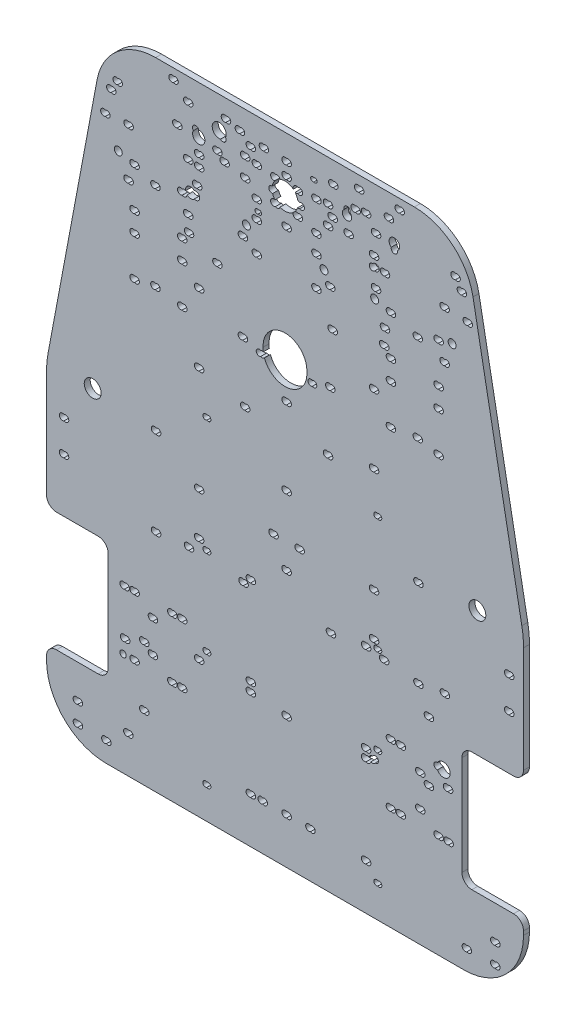
SolidWorks part; units mm, degrees
ref_plane "前视基准面" through (0, 0, 0) normal (0, 0, 1) x (1, 0, 0)
ref_plane "上视基准面" through (0, 0, 0) normal (0, 1, 0) x (1, 0, 0)
ref_plane "右视基准面" through (0, 0, 0) normal (1, 0, 0) x (0, 0, -1)
other "Configuration Table"
sketch "草图1" plane through (0, 0, 0) normal (0, 0, 1) x (1, 0, 0)
  line L0 (-120, -4.645) -> (-120, -58.035)
  line L1 (-94, -63.035) -> (-115, -63.035)
  line L2 (-119.145, 4.565) -> (-94.59, 135.53)
  line L3 (-89, -118.035) -> (-89, -68.035)
  line L4 (65.1, 160) -> (-65.1, 160)
  line L5 (-115, -123.035) -> (-94, -123.035)
  line L6 (94.59, 135.53) -> (119.145, 4.565)
  line L7 (-120, -128.035) -> (-120, -130)
  line L8 (120, -58.035) -> (120, -4.645)
  line L9 (-90, -160) -> (90, -160)
  line L10 (115, -63.035) -> (94, -63.035)
  line L11 (120, -130) -> (120, -128.035)
  line L12 (89, -68.035) -> (89, -118.035)
  line L13 (94, -123.035) -> (115, -123.035)
  arc A0 (-120, -58.035) -> (-115, -63.035) centre (-115, -58.035) ccw
  arc A1 (-119.145, 4.565) -> (-120, -4.645) centre (-70, -4.642) ccw
  arc A2 (-89, -68.035) -> (-94, -63.035) centre (-94, -68.035) ccw
  arc A3 (-65.1, 160) -> (-94.59, 135.53) centre (-65.1041, 130) ccw
  arc A4 (-94, -123.035) -> (-89, -118.035) centre (-94, -118.035) ccw
  arc A5 (94.59, 135.53) -> (65.1, 160) centre (65.1041, 130) ccw
  arc A6 (-115, -123.035) -> (-120, -128.035) centre (-115, -128.035) ccw
  arc A7 (120, -4.645) -> (119.145, 4.565) centre (70, -4.642) ccw
  arc A8 (-120, -130) -> (-90, -160) centre (-90, -130) ccw
  arc A9 (115, -63.035) -> (120, -58.035) centre (115, -58.035) ccw
  arc A10 (90, -160) -> (120, -130) centre (90, -130) ccw
  arc A11 (94, -63.035) -> (89, -68.035) centre (94, -68.035) ccw
  arc A12 (120, -128.035) -> (115, -123.035) centre (115, -128.035) ccw
  arc A13 (89, -118.035) -> (94, -123.035) centre (94, -118.035) ccw
extrude "底盘板_3mm" add sketch "草图1" along normal blind 3
sketch "草图2" plane through (0, 0, 0) normal (0, 0, 1) x (1, 0, 0)
  circle A0 centre (71.6222, -88.447) radius 1.6
  circle A1 centre (71.6222, -58.447) radius 1.6
  circle A2 centre (-18, -88.05) radius 1.6
  circle A3 centre (79.5, 99.85) radius 1.6
  circle A4 centre (-44, -38.5574) radius 1.6
  circle A5 centre (-44, -91.3574) radius 1.6
  circle A6 centre (-18, -43.55) radius 1.6
  circle A7 centre (-81.25, -100.9) radius 1.6
  circle A8 centre (49.5, 99.85) radius 1.6
  circle A9 centre (-15, 99.8501) radius 1.6
  circle A10 centre (44, -38.5574) radius 1.6
  circle A11 centre (-18, -137.05) radius 1.6
  circle A12 centre (79.6222, -44.447) radius 1.6
  circle A13 centre (79.5, 123.85) radius 1.6
  circle A14 centre (-44, 70.4426) radius 1.6
  circle A15 centre (-44, -17.0574) radius 1.6
  circle A16 centre (-15, 123.8501) radius 1.6
  circle A17 centre (44, 123.2426) radius 1.6
  circle A18 centre (5.6569, 137.8532) radius 1.6
  circle A19 centre (40, -92.55) radius 1.6
  circle A20 centre (-18, -92.55) radius 1.6
  circle A21 centre (44, -17.0574) radius 1.6
  circle A22 centre (49.5, 123.85) radius 1.6
  circle A23 centre (40, 145.2) radius 1.6
  circle A24 centre (44, -91.3574) radius 1.6
  circle A25 centre (40, -88.05) radius 1.6
  circle A26 centre (-5.6569, 137.8532) radius 1.6
  circle A27 centre (31.2, 141.8053) radius 1.6
  circle A28 centre (44, 35.7426) radius 1.6
  circle A29 centre (-79.5, 99.8501) radius 1.6
  circle A30 centre (15, 138.85) radius 1.6
  circle A31 centre (-6.5532, 131.7498) radius 1.6
  circle A32 centre (-79.6222, -141.3529) radius 1.6
  circle A33 centre (36.5, 153.85) radius 1.6
  circle A34 centre (40, -137.05) radius 1.6
  circle A35 centre (44, 70.4426) radius 1.6
  circle A36 centre (-5.6569, 126.5394) radius 1.6
  circle A37 centre (15, 123.85) radius 1.6
  circle A38 centre (-18, 145.2) radius 1.6
  circle A39 centre (-23.5, 149.4184) radius 1.6
  circle A40 centre (5.6569, 126.5394) radius 1.6
  circle A41 centre (45, 138.85) radius 1.6
  circle A42 centre (-79.5, 123.8501) radius 1.6
  circle A43 centre (15, 99.85) radius 1.6
  circle A44 centre (40, -43.55) radius 1.6
  circle A45 centre (-15, 138.85) radius 1.6
  circle A46 centre (6.5532, 131.7498) radius 1.6
  circle A47 centre (-71.6222, -127.3529) radius 1.6
  circle A48 centre (-71.6222, -97.3529) radius 1.6
  circle A49 centre (55, 136.201) radius 1.6
  circle A50 centre (81.25, -84.9) radius 1.6
  circle A51 centre (-49.5, 148.85) radius 1.6
  circle A52 centre (-30.5, 150.85) radius 1.6
  circle A53 centre (-44, 123.2426) radius 1.6
  circle A54 centre (15, 114.85) radius 1.6
  circle A55 centre (0, 132.1963) radius 4
  circle A56 centre (-20.8597, 130.0559) radius 1.6
  circle A57 centre (0, 119.1612) radius 1.6
  circle A58 centre (23.5, 149.4184) radius 1.6
  circle A59 centre (-44, 35.7426) radius 1.6
  circle A60 centre (31.2, 131.8058) radius 1.6
  circle A61 centre (51.5, 148.85) radius 1.6
  circle A62 centre (-14, 118.5695) radius 1.1
  circle A63 centre (20.8597, 130.0559) radius 1.6
  circle A64 centre (-34.7189, 144.2392) radius 1.6
  circle A65 centre (-49.5, 123.8501) radius 1.6
  circle A66 centre (45, 114.85) radius 1.6
  circle A67 centre (-55, 136.201) radius 1.6
  circle A68 centre (-45, 114.85) radius 1.6
  circle A69 centre (14.0014, 146.5709) radius 1.1
  circle A70 centre (0.0007, 147.5702) radius 1.6
  circle A71 centre (-31.2, 141.8053) radius 1.6
  circle A72 centre (34.7189, 144.2392) radius 1.6
  circle A73 centre (44, 128.7426) radius 1.6
  circle A74 centre (-11.4, 147.9509) radius 1.6
  circle A75 centre (-20.8597, 139.5559) radius 1.6
  circle A76 centre (46, -85.9817) radius 1.35
  circle A77 centre (105, -140) radius 1.6
  circle A78 centre (-15, 114.85) radius 1.6
  circle A79 centre (-45, 138.85) radius 1.6
  circle A80 centre (20.8597, 139.5559) radius 1.6
  circle A81 centre (-31.2, 131.8058) radius 1.6
  circle A82 centre (-40, -85.9817) radius 1.35
  circle A83 centre (-85, 140) radius 1.6
  circle A84 centre (85, 140) radius 1.6
  circle A85 centre (-40, -143.9817) radius 1.35
  circle A86 centre (46, 16.0183) radius 1.35
  circle A87 centre (46, -143.9817) radius 1.35
  circle A88 centre (-105, -140) radius 1.6
  circle A89 centre (96.7802, 0) radius 4.25
  circle A90 centre (46, -41.9817) radius 1.35
  circle A91 centre (-81.5003, -78.0344) radius 1.6
  circle A92 centre (-57.5003, -78.0343) radius 1.6
  circle A93 centre (52.5, -77.9) radius 1.6
  circle A94 centre (-76.5, -107.9) radius 1.6
  circle A95 centre (-40, -41.9817) radius 1.35
  circle A96 centre (-52.5, -107.9) radius 1.6
  circle A97 centre (-81.5001, -108.0344) radius 1.6
  circle A98 centre (57.5001, -108.0343) radius 1.6
  circle A99 centre (67.25, -84.9) radius 1.6
  circle A100 centre (-96.7802, 0) radius 4.25
  circle A101 centre (-52.5, -77.9) radius 1.6
  circle A102 centre (-76.5, -77.9) radius 1.6
  circle A103 centre (81.5001, -108.0344) radius 1.6
  circle A104 centre (67.25, -100.9) radius 1.6
  circle A105 centre (76.5, -77.9) radius 1.6
  circle A106 centre (81.5003, -78.0344) radius 1.6
  circle A107 centre (12, -137.0155) radius 1.6
  circle A108 centre (-67.25, -84.9) radius 1.6
  circle A109 centre (-57.5001, -108.0343) radius 1.6
  circle A110 centre (-40, 16.0183) radius 1.35
  circle A111 centre (112, -36.0494) radius 1.6
  circle A112 centre (-90.691, -150) radius 1.6
  circle A113 centre (105, -150) radius 1.6
  circle A114 centre (112, -19.9702) radius 1.6
  circle A115 centre (-67.25, -100.9) radius 1.6
  circle A116 centre (0, -137.0155) radius 1.6
  circle A117 centre (-105, -150) radius 1.6
  circle A118 centre (91.157, 123.1269) radius 1.6
  circle A119 centre (-112, -36.0494) radius 1.6
  circle A120 centre (22, 60.2034) radius 1.6
  circle A121 centre (76.5, -107.9) radius 1.6
  circle A122 centre (23.202, 134.9205) radius 1.6
  circle A123 centre (-112, -19.9702) radius 1.6
  circle A124 centre (56.9, 155) radius 1.6
  circle A125 centre (-91.157, 123.1269) radius 1.6
  circle A126 centre (66.3284, -46.618) radius 1.6
  circle A127 centre (90.691, -150) radius 1.6
  circle A128 centre (-65.6716, -46.618) radius 1.6
  circle A129 centre (-66, 60.2034) radius 1.6
  circle A130 centre (-56.9, 155) radius 1.6
  circle A131 centre (88.2, 134.9846) radius 1.6
  circle A132 centre (-22, 60.2034) radius 1.6
  circle A133 centre (66.3284, -2.618) radius 1.6
  circle A134 centre (57.5003, -78.0343) radius 1.6
  circle A135 centre (23.202, 85.9205) radius 1.6
  circle A136 centre (-88.2, 134.9846) radius 1.6
  circle A137 centre (22, 104.2034) radius 1.6
  circle A138 centre (52.5, 108.1) radius 1.6
  circle A139 centre (76.5, 58.1) radius 1.6
  circle A140 centre (-66, 104.2034) radius 1.6
  circle A141 centre (66, 60.2034) radius 1.6
  circle A142 centre (-76.5, 108.1) radius 1.6
  circle A143 centre (52.5, 78.1) radius 1.6
  circle A144 centre (76.5, 78.1) radius 1.6
  circle A145 centre (-12, -137.0155) radius 1.6
  circle A146 centre (-76.5, 88.1) radius 1.6
  circle A147 centre (76.5, 88.1) radius 1.6
  circle A148 centre (-76.5, 58.1) radius 1.6
  circle A149 centre (-34.798, 85.9205) radius 1.6
  circle A150 centre (52.5, -107.9) radius 1.6
  circle A151 centre (76.5, 108.1) radius 1.6
  circle A152 centre (-52.5, 88.1) radius 1.6
  circle A153 centre (49.1, 92.0723) radius 1.6
  circle A154 centre (-52.5, 58.1) radius 1.6
  circle A155 centre (-65.6716, -2.618) radius 1.6
  circle A156 centre (-52.5, 78.1) radius 1.6
  circle A157 centre (0, 61.5723) radius 11
  circle A158 centre (66, 104.2034) radius 1.6
  circle A159 centre (-52.5, 108.1) radius 1.6
  circle A160 centre (-83.8997, 109.9166) radius 2
  circle A161 centre (-76.5, 78.1) radius 1.6
  circle A162 centre (-49.1, 92.0723) radius 1.6
  circle A163 centre (-20.8597, 30.2366) radius 1.6
  circle A164 centre (6.5532, -17.9502) radius 1.6
  circle A165 centre (52.5, 88.1) radius 1.6
  circle A166 centre (-22, 104.2034) radius 1.6
  circle A167 centre (-44.9, 109.9168) radius 2
  circle A168 centre (0, -94.0277) radius 1.6
  circle A169 centre (-34.798, 134.9205) radius 1.6
  circle A170 centre (12.9911, 57.4701) radius 1.5
  circle A171 centre (19.6002, 109.9172) radius 2
  circle A172 centre (20.8597, 30.2366) radius 1.6
  circle A173 centre (-6.5532, -17.9502) radius 1.6
  circle A174 centre (0, 4.1723) radius 1.6
  circle A175 centre (0, 42.9723) radius 1.6
  circle A176 centre (0, -30.5388) radius 1.6
  circle A177 centre (-44, 128.7426) radius 1.6
  circle A178 centre (-49.5, 99.8501) radius 1.6
  circle A179 centre (-21.6716, -46.618) radius 1.6
  circle A180 centre (0, 141.1723) radius 1.6
  circle A181 centre (-49.1, -44.9277) radius 1.6
  circle A182 centre (52.5, 58.1) radius 1.6
  circle A183 centre (45.1002, 109.9173) radius 2
  circle A184 centre (-12.9897, 57.4702) radius 1.5
  circle A185 centre (84.0999, 109.9175) radius 2
  circle A186 centre (22.3284, -46.618) radius 1.6
  circle A187 centre (49.1, -44.9277) radius 1.6
  circle A188 centre (-19.3995, 109.917) radius 2
extrude "切除-拉伸3" cut sketch "草图2" along normal through all
sketch "草图741" plane through (0, 0, 0) normal (0, 0, 1) x (1, 0, 0)
  circle A0 centre (73.2222, -88.447) radius 1.6
  circle A1 centre (71.6222, -88.447) radius 1.6 construction
  circle A2 centre (73.2222, -58.447) radius 1.6
  circle A3 centre (71.6222, -58.447) radius 1.6 construction
  circle A4 centre (-16.4, -88.05) radius 1.6
  circle A5 centre (-18, -88.05) radius 1.6 construction
  circle A6 centre (81.1, 99.85) radius 1.6
  circle A7 centre (79.5, 99.85) radius 1.6 construction
  circle A8 centre (-42.4, -38.5574) radius 1.6
  circle A9 centre (-44, -38.5574) radius 1.6 construction
  circle A10 centre (-42.4, -91.3574) radius 1.6
  circle A11 centre (-44, -91.3574) radius 1.6 construction
  circle A12 centre (-16.4, -43.55) radius 1.6
  circle A13 centre (-18, -43.55) radius 1.6 construction
  circle A14 centre (-79.65, -100.9) radius 1.6
  circle A15 centre (-81.25, -100.9) radius 1.6 construction
  circle A16 centre (51.1, 99.85) radius 1.6
  circle A17 centre (49.5, 99.85) radius 1.6 construction
  circle A18 centre (-13.4, 99.8501) radius 1.6
  circle A19 centre (-15, 99.8501) radius 1.6 construction
  circle A20 centre (45.6, -38.5574) radius 1.6
  circle A21 centre (44, -38.5574) radius 1.6 construction
  circle A22 centre (-16.4, -137.05) radius 1.6
  circle A23 centre (-18, -137.05) radius 1.6 construction
  circle A24 centre (81.2222, -44.447) radius 1.6
  circle A25 centre (79.6222, -44.447) radius 1.6 construction
  circle A26 centre (81.1, 123.85) radius 1.6
  circle A27 centre (79.5, 123.85) radius 1.6 construction
  circle A28 centre (-42.4, 70.4426) radius 1.6
  circle A29 centre (-44, 70.4426) radius 1.6 construction
  circle A30 centre (-42.4, -17.0574) radius 1.6
  circle A31 centre (-44, -17.0574) radius 1.6 construction
  circle A32 centre (-13.4, 123.8501) radius 1.6
  circle A33 centre (-15, 123.8501) radius 1.6 construction
  circle A34 centre (45.6, 123.85) radius 1.7114
  circle A35 centre (7.2569, 137.8532) radius 1.6
  circle A36 centre (5.6569, 137.8532) radius 1.6 construction
  circle A37 centre (41.6, -92.55) radius 1.6
  circle A38 centre (40, -92.55) radius 1.6 construction
extrude "切除-拉伸741" cut sketch "草图741" along normal through all
sketch "草图742" plane through (0, 0, 0) normal (0, 0, 1) x (1, 0, 0)
  circle A0 centre (-16.4, -92.55) radius 1.6
  circle A1 centre (-18, -92.55) radius 1.6 construction
  circle A2 centre (45.6, -17.0574) radius 1.6
  circle A3 centre (44, -17.0574) radius 1.6 construction
  circle A4 centre (51.1, 123.85) radius 1.6
  circle A5 centre (49.5, 123.85) radius 1.6 construction
  circle A6 centre (41.6, 145.2) radius 1.6
  circle A7 centre (40, 145.2) radius 1.6 construction
  circle A8 centre (45.4329, -90.6454) radius 1.6
  arc A9 (43.1891, -92.7367) -> (42.4109, -91.1707) centre (44, -91.3574) ccw construction
  circle A10 centre (41.6, -88.05) radius 1.6
  circle A11 centre (40, -88.05) radius 1.6 construction
  circle A12 centre (-4.0569, 137.8532) radius 1.6
  circle A13 centre (-5.6569, 137.8532) radius 1.6 construction
  circle A14 centre (31.2, 139.4532) radius 2.3521
  circle A15 centre (45.6, 35.7426) radius 1.6
  circle A16 centre (-77.9, 99.8501) radius 1.6
  circle A17 centre (-79.5, 99.8501) radius 1.6 construction
  circle A18 centre (16.6, 138.85) radius 1.6
  circle A19 centre (15, 138.85) radius 1.6 construction
  circle A20 centre (-4.9532, 131.7498) radius 1.6
  circle A21 centre (-6.5532, 131.7498) radius 1.6 construction
  circle A22 centre (-78.0222, -141.3529) radius 1.6
  circle A23 centre (-79.6222, -141.3529) radius 1.6 construction
  circle A24 centre (38.1, 153.85) radius 1.6
  circle A25 centre (36.5, 153.85) radius 1.6 construction
  circle A26 centre (41.6, -137.05) radius 1.6
  circle A27 centre (45.6, 70.4426) radius 1.6
  circle A28 centre (44, 70.4426) radius 1.6 construction
  circle A29 centre (-4.0569, 126.5394) radius 1.6
  circle A30 centre (-5.6569, 126.5394) radius 1.6 construction
  circle A31 centre (16.6, 123.85) radius 1.6
  circle A32 centre (15, 123.85) radius 1.6 construction
  circle A33 centre (-16.4, 145.2) radius 1.6
  circle A34 centre (-18, 145.2) radius 1.6 construction
  circle A35 centre (-21.9, 149.4184) radius 1.6
  circle A36 centre (-23.5, 149.4184) radius 1.6 construction
extrude "切除-拉伸742" cut sketch "草图742" along normal through all
sketch "草图744" plane through (0, 0, 0) normal (0, 0, 1) x (1, 0, 0)
  circle A0 centre (7.2569, 126.5394) radius 1.6
  circle A1 centre (5.6569, 126.5394) radius 1.6 construction
  circle A2 centre (46.6, 138.85) radius 1.6
  circle A3 centre (45, 138.85) radius 1.6 construction
  circle A4 centre (-77.9, 123.8501) radius 1.6
  circle A5 centre (-79.5, 123.8501) radius 1.6 construction
  circle A6 centre (16.6, 99.85) radius 1.6
  circle A7 centre (15, 99.85) radius 1.6 construction
  circle A8 centre (41.6, -43.55) radius 1.6
  circle A9 centre (40, -43.55) radius 1.6 construction
  circle A10 centre (-13.4, 138.85) radius 1.6
  circle A11 centre (-15, 138.85) radius 1.6 construction
  circle A12 centre (8.1532, 131.7498) radius 1.6
  circle A13 centre (6.5532, 131.7498) radius 1.6 construction
  circle A14 centre (-70.0222, -127.3529) radius 1.6
  circle A15 centre (-71.6222, -127.3529) radius 1.6 construction
  circle A16 centre (-70.0222, -97.3529) radius 1.6
  circle A17 centre (-71.6222, -97.3529) radius 1.6 construction
  circle A18 centre (55, 138.85) radius 2.649
extrude "切除-拉伸744" cut sketch "草图744" along normal through all
sketch "草图745" plane through (0, 0, 0) normal (0, 0, 1) x (1, 0, 0)
  circle A0 centre (82.85, -84.9) radius 1.6
  circle A1 centre (81.25, -84.9) radius 1.6 construction
  circle A2 centre (-47.9, 148.85) radius 1.6
  circle A3 centre (-49.5, 148.85) radius 1.6 construction
  circle A4 centre (-28.9, 150.85) radius 1.6
  circle A5 centre (-30.5, 150.85) radius 1.6 construction
  circle A6 centre (-42.4, 123.2426) radius 1.6
  circle A7 centre (-44, 123.2426) radius 1.6 construction
  circle A8 centre (16.6, 114.85) radius 1.6
  circle A9 centre (15, 114.85) radius 1.6 construction
  circle A10 centre (0, 132.1963) radius 6.5684
  circle A11 centre (-19.2597, 130.0559) radius 1.6
  circle A12 centre (-20.8597, 130.0559) radius 1.6 construction
  circle A13 centre (1.6, 119.1612) radius 1.6
  circle A14 centre (0, 119.1612) radius 1.6 construction
  circle A15 centre (25.1, 149.4184) radius 1.6
  circle A16 centre (23.5, 149.4184) radius 1.6 construction
  circle A17 centre (-42.4, 35.7426) radius 1.6
  circle A18 centre (-44, 35.7426) radius 1.6 construction
extrude "切除-拉伸745" cut sketch "草图745" along normal through all
sketch "草图746" plane through (0, 0, 0) normal (0, 0, 1) x (1, 0, 0)
  circle A0 centre (32.8, 131.8058) radius 1.6
  circle A1 centre (31.2, 131.8058) radius 1.6 construction
  circle A2 centre (53.1, 148.85) radius 1.6
  circle A3 centre (51.5, 148.85) radius 1.6 construction
  circle A4 centre (-12.9, 118.5695) radius 1.1
  circle A5 centre (-14, 118.5695) radius 1.1 construction
  circle A6 centre (22.4597, 130.0559) radius 1.6
  circle A7 centre (20.8597, 130.0559) radius 1.6 construction
  circle A8 centre (-33.1189, 144.2392) radius 1.6
  circle A9 centre (-34.7189, 144.2392) radius 1.6 construction
  circle A10 centre (-47.9, 123.8501) radius 1.6
  circle A11 centre (-49.5, 123.8501) radius 1.6 construction
  circle A12 centre (46.6, 114.85) radius 1.6
  circle A13 centre (45, 114.85) radius 1.6 construction
  circle A14 centre (-53.4, 136.201) radius 1.6
  circle A15 centre (-55, 136.201) radius 1.6 construction
  circle A16 centre (-43.4, 114.85) radius 1.6
  circle A17 centre (-45, 114.85) radius 1.6 construction
  circle A18 centre (15.1014, 146.5709) radius 1.1
  circle A19 centre (14.0014, 146.5709) radius 1.1 construction
  circle A20 centre (1.6007, 147.5702) radius 1.6
  circle A21 centre (0.0007, 147.5702) radius 1.6 construction
  circle A22 centre (-33.1189, 144.2392) radius 3.5189
  circle A23 centre (36.3189, 144.2392) radius 1.6
  circle A24 centre (34.7189, 144.2392) radius 1.6 construction
  circle A25 centre (45.6, 128.7426) radius 1.6
  circle A26 centre (44, 128.7426) radius 1.6 construction
  circle A27 centre (-9.8, 147.9509) radius 1.6
  circle A28 centre (-11.4, 147.9509) radius 1.6 construction
  circle A29 centre (-19.2597, 139.5559) radius 1.6
  circle A30 centre (-20.8597, 139.5559) radius 1.6 construction
  circle A31 centre (47.35, -85.9817) radius 1.35
  circle A32 centre (46, -85.9817) radius 1.35 construction
  circle A33 centre (106.6, -140) radius 1.6
  circle A34 centre (105, -140) radius 1.6 construction
  circle A35 centre (-13.4, 114.85) radius 1.6
  circle A36 centre (-15, 114.85) radius 1.6 construction
  circle A37 centre (-43.4, 136.201) radius 3.0947
extrude "切除-拉伸746" cut sketch "草图746" along normal through all
sketch "草图747" plane through (0, 0, 0) normal (0, 0, 1) x (1, 0, 0)
  circle A0 centre (22.4597, 139.5559) radius 1.6
  circle A1 centre (20.8597, 139.5559) radius 1.6 construction
  circle A2 centre (-29.6, 131.8058) radius 1.6
  circle A3 centre (-31.2, 131.8058) radius 1.6 construction
  circle A4 centre (-38.65, -85.9817) radius 1.35
  circle A5 centre (-40, -85.9817) radius 1.35 construction
  circle A6 centre (-83.4, 140) radius 1.6
  circle A7 centre (-85, 140) radius 1.6 construction
  circle A8 centre (86.6, 140) radius 1.6
  circle A9 centre (85, 140) radius 1.6 construction
  circle A10 centre (-38.65, -143.9817) radius 1.35
  circle A11 centre (-40, -143.9817) radius 1.35 construction
  circle A12 centre (47.35, 16.0183) radius 1.35
  circle A13 centre (46, 16.0183) radius 1.35 construction
  circle A14 centre (47.35, -143.9817) radius 1.35
  circle A15 centre (46, -143.9817) radius 1.35 construction
  circle A16 centre (-103.4, -140) radius 1.6
  circle A17 centre (-105, -140) radius 1.6 construction
  circle A18 centre (96.7802, 0) radius 4.25
  circle A19 centre (47.35, -41.9817) radius 1.35
  circle A20 centre (46, -41.9817) radius 1.35 construction
  circle A21 centre (-79.9003, -78.0344) radius 1.6
  circle A22 centre (-81.5003, -78.0344) radius 1.6 construction
  circle A23 centre (-55.9003, -78.0343) radius 1.6
  circle A24 centre (-57.5003, -78.0343) radius 1.6 construction
  circle A25 centre (54.1, -77.9) radius 1.6
  circle A26 centre (52.5, -77.9) radius 1.6 construction
  circle A27 centre (-74.9, -107.9) radius 1.6
  circle A28 centre (-76.5, -107.9) radius 1.6 construction
  circle A29 centre (-38.65, -41.9817) radius 1.35
  circle A30 centre (-40, -41.9817) radius 1.35 construction
  circle A31 centre (-50.9, -107.9) radius 1.6
  circle A32 centre (-52.5, -107.9) radius 1.6 construction
  circle A33 centre (59.1001, -108.0343) radius 1.6
  circle A34 centre (57.5001, -108.0343) radius 1.6 construction
  circle A35 centre (68.85, -84.9) radius 1.6
  circle A36 centre (67.25, -84.9) radius 1.6 construction
extrude "切除-拉伸747" cut sketch "草图747" along normal through all
sketch "草图748" plane through (0, 0, 0) normal (0, 0, 1) x (1, 0, 0)
  circle A0 centre (-96.7802, 0) radius 4.25
  circle A1 centre (-50.9, -77.9) radius 1.6
  circle A2 centre (-52.5, -77.9) radius 1.6 construction
  circle A3 centre (-74.9, -77.9) radius 1.6
  circle A4 centre (-76.5, -77.9) radius 1.6 construction
  circle A5 centre (83.1001, -108.0344) radius 1.6
  circle A6 centre (81.5001, -108.0344) radius 1.6 construction
  circle A7 centre (68.85, -100.9) radius 1.6
  circle A8 centre (67.25, -100.9) radius 1.6 construction
  circle A9 centre (78.1, -77.9) radius 1.6
  circle A10 centre (76.5, -77.9) radius 1.6 construction
  circle A11 centre (79.7, -77.9) radius 3.4001
  circle A12 centre (13.6, -137.0155) radius 1.6
  circle A13 centre (12, -137.0155) radius 1.6 construction
  circle A14 centre (-65.65, -84.9) radius 1.6
  circle A15 centre (-67.25, -84.9) radius 1.6 construction
  circle A16 centre (-55.9001, -108.0343) radius 1.6
  circle A17 centre (-57.5001, -108.0343) radius 1.6 construction
  circle A18 centre (-38.65, 16.0183) radius 1.35
  circle A19 centre (-40, 16.0183) radius 1.35 construction
  circle A20 centre (113.6, -36.0494) radius 1.6
  circle A21 centre (112, -36.0494) radius 1.6 construction
  circle A22 centre (-89.091, -150) radius 1.6
  circle A23 centre (-90.691, -150) radius 1.6 construction
  circle A24 centre (106.6, -150) radius 1.6
  circle A25 centre (105, -150) radius 1.6 construction
  circle A26 centre (113.6, -19.9702) radius 1.6
  circle A27 centre (112, -19.9702) radius 1.6 construction
  circle A28 centre (-65.65, -100.9) radius 1.6
  circle A29 centre (-67.25, -100.9) radius 1.6 construction
  circle A30 centre (1.6, -137.0155) radius 1.6
  circle A31 centre (0, -137.0155) radius 1.6 construction
  circle A32 centre (-103.4, -150) radius 1.6
  circle A33 centre (-105, -150) radius 1.6 construction
  circle A34 centre (92.757, 123.1269) radius 1.6
  circle A35 centre (91.157, 123.1269) radius 1.6 construction
  circle A36 centre (-110.4, -36.0494) radius 1.6
  circle A37 centre (-112, -36.0494) radius 1.6 construction
extrude "切除-拉伸748" cut sketch "草图748" along normal through all
sketch "草图749" plane through (0, 0, 0) normal (0, 0, 1) x (1, 0, 0)
  circle A0 centre (23.6, 60.2034) radius 1.6
  circle A1 centre (22, 60.2034) radius 1.6 construction
  circle A2 centre (78.1, -107.9) radius 1.6
  circle A3 centre (76.5, -107.9) radius 1.6 construction
  circle A4 centre (24.802, 134.9205) radius 1.6
  circle A5 centre (23.202, 134.9205) radius 1.6 construction
  circle A6 centre (-110.4, -19.9702) radius 1.6
  circle A7 centre (-112, -19.9702) radius 1.6 construction
  circle A8 centre (58.5, 155) radius 1.6
  circle A9 centre (56.9, 155) radius 1.6 construction
  circle A10 centre (-89.557, 123.1269) radius 1.6
  circle A11 centre (-91.157, 123.1269) radius 1.6 construction
  circle A12 centre (67.9284, -46.618) radius 1.6
  circle A13 centre (66.3284, -46.618) radius 1.6 construction
  circle A14 centre (92.291, -150) radius 1.6
  circle A15 centre (90.691, -150) radius 1.6 construction
  circle A16 centre (-64.0716, -46.618) radius 1.6
  circle A17 centre (-65.6716, -46.618) radius 1.6 construction
  circle A18 centre (-64.4, 60.2034) radius 1.6
  circle A19 centre (-66, 60.2034) radius 1.6 construction
  circle A20 centre (-55.3, 155) radius 1.6
  circle A21 centre (-56.9, 155) radius 1.6 construction
  circle A22 centre (89.8, 134.9846) radius 1.6
  circle A23 centre (88.2, 134.9846) radius 1.6 construction
  circle A24 centre (-20.4, 60.2034) radius 1.6
  circle A25 centre (-22, 60.2034) radius 1.6 construction
  circle A26 centre (67.9284, -2.618) radius 1.6
  circle A27 centre (66.3284, -2.618) radius 1.6 construction
  circle A28 centre (59.1003, -78.0343) radius 1.6
  circle A29 centre (57.5003, -78.0343) radius 1.6 construction
  circle A30 centre (24.802, 85.9205) radius 1.6
  circle A31 centre (23.202, 85.9205) radius 1.6 construction
  circle A32 centre (-86.6, 134.9846) radius 1.6
  circle A33 centre (-88.2, 134.9846) radius 1.6 construction
  circle A34 centre (23.6, 104.2034) radius 1.6
  circle A35 centre (22, 104.2034) radius 1.6 construction
  circle A36 centre (54.1, 108.1) radius 1.6
  circle A37 centre (52.5, 108.1) radius 1.6 construction
  circle A38 centre (78.1, 58.1) radius 1.6
  circle A39 centre (76.5, 58.1) radius 1.6 construction
extrude "切除-拉伸749" cut sketch "草图749" along normal through all
sketch "草图750" plane through (0, 0, 0) normal (0, 0, 1) x (1, 0, 0)
  circle A0 centre (-64.4, 104.2034) radius 1.6
  circle A1 centre (-66, 104.2034) radius 1.6 construction
  circle A2 centre (67.6, 60.2034) radius 1.6
  circle A3 centre (66, 60.2034) radius 1.6 construction
  circle A4 centre (-74.9, 108.1) radius 1.6
  circle A5 centre (-76.5, 108.1) radius 1.6 construction
  circle A6 centre (54.1, 78.1) radius 1.6
  circle A7 centre (52.5, 78.1) radius 1.6 construction
  circle A8 centre (78.1, 78.1) radius 1.6
  circle A9 centre (76.5, 78.1) radius 1.6 construction
  circle A10 centre (-10.4, -137.0155) radius 1.6
  circle A11 centre (-12, -137.0155) radius 1.6 construction
  circle A12 centre (-74.9, 88.1) radius 1.6
  circle A13 centre (-76.5, 88.1) radius 1.6 construction
  circle A14 centre (78.1, 88.1) radius 1.6
  circle A15 centre (76.5, 88.1) radius 1.6 construction
  circle A16 centre (-74.9, 58.1) radius 1.6
  circle A17 centre (-76.5, 58.1) radius 1.6 construction
  circle A18 centre (-33.198, 85.9205) radius 1.6
  circle A19 centre (-34.798, 85.9205) radius 1.6 construction
  circle A20 centre (54.1, -107.9) radius 1.6
  circle A21 centre (52.5, -107.9) radius 1.6 construction
  circle A22 centre (78.1, 108.1) radius 1.6
  circle A23 centre (76.5, 108.1) radius 1.6 construction
  circle A24 centre (-50.9, 88.1) radius 1.6
  circle A25 centre (-52.5, 88.1) radius 1.6 construction
  circle A26 centre (50.7, 92.0723) radius 1.6
  circle A27 centre (49.1, 92.0723) radius 1.6 construction
  circle A28 centre (-50.9, 58.1) radius 1.6
  circle A29 centre (-52.5, 58.1) radius 1.6 construction
  circle A30 centre (-64.0716, -2.618) radius 1.6
  circle A31 centre (-65.6716, -2.618) radius 1.6 construction
  circle A32 centre (-50.9, 78.1) radius 1.6
  circle A33 centre (-52.5, 78.1) radius 1.6 construction
  circle A34 centre (0, 60.2034) radius 11
  circle A35 centre (67.6, 104.2034) radius 1.6
  circle A36 centre (66, 104.2034) radius 1.6 construction
  circle A37 centre (-50.9, 108.1) radius 1.6
  circle A38 centre (-52.5, 108.1) radius 1.6 construction
extrude "切除-拉伸750" cut sketch "草图750" along normal through all
sketch "草图751" plane through (0, 0, 0) normal (0, 0, 1) x (1, 0, 0)
  circle A0 centre (-74.9, 78.1) radius 1.6
  circle A1 centre (-76.5, 78.1) radius 1.6 construction
  circle A2 centre (-47.5, 92.0723) radius 1.6
  circle A3 centre (-49.1, 92.0723) radius 1.6 construction
  circle A4 centre (-19.2597, 30.2366) radius 1.6
  circle A5 centre (-20.8597, 30.2366) radius 1.6 construction
  circle A6 centre (8.1532, -17.9502) radius 1.6
  circle A7 centre (6.5532, -17.9502) radius 1.6 construction
  circle A8 centre (54.1, 88.1) radius 1.6
  circle A9 centre (52.5, 88.1) radius 1.6 construction
  circle A10 centre (-20.4, 104.2034) radius 1.6
  circle A11 centre (-22, 104.2034) radius 1.6 construction
  circle A12 centre (-47.5, 109.9168) radius 2.6
  circle A13 centre (1.6, -94.0277) radius 1.6
  circle A14 centre (0, -94.0277) radius 1.6 construction
  circle A15 centre (-33.198, 134.9205) radius 1.6
  circle A16 centre (-34.798, 134.9205) radius 1.6 construction
  circle A17 centre (14.4911, 57.4701) radius 1.5
  circle A18 centre (12.9911, 57.4701) radius 1.5 construction
  circle A19 centre (19.6002, 109.9168) radius 0.0004
  circle A20 centre (22.4597, 30.2366) radius 1.6
  circle A21 centre (20.8597, 30.2366) radius 1.6 construction
  circle A22 centre (-4.9532, -17.9502) radius 1.6
  circle A23 centre (-6.5532, -17.9502) radius 1.6 construction
  circle A24 centre (1.6, 4.1723) radius 1.6
  circle A25 centre (0, 4.1723) radius 1.6 construction
  circle A26 centre (1.6, 42.9723) radius 1.6
  circle A27 centre (0, 42.9723) radius 1.6 construction
  circle A28 centre (1.6, -30.5388) radius 1.6
  circle A29 centre (0, -30.5388) radius 1.6 construction
  circle A30 centre (-42.4, 128.7426) radius 1.6
  circle A31 centre (-44, 128.7426) radius 1.6 construction
  circle A32 centre (-47.9, 99.8501) radius 1.6
  circle A33 centre (-49.5, 99.8501) radius 1.6 construction
  circle A34 centre (-20.0716, -46.618) radius 1.6
  circle A35 centre (-21.6716, -46.618) radius 1.6 construction
extrude "切除-拉伸751" cut sketch "草图751" along normal through all
sketch "草图752" plane through (0, 0, 0) normal (0, 0, 1) x (1, 0, 0)
  circle A0 centre (1.6, 141.1723) radius 1.6
  circle A1 centre (0, 141.1723) radius 1.6 construction
  circle A2 centre (-47.5, -44.9277) radius 1.6
  circle A3 centre (-49.1, -44.9277) radius 1.6 construction
  circle A4 centre (54.1, 58.1) radius 1.6
  circle A5 centre (52.5, 58.1) radius 1.6 construction
  circle A6 centre (-11.4897, 57.4702) radius 1.5
  circle A7 centre (-12.9897, 57.4702) radius 1.5 construction
  circle A8 centre (23.9284, -46.618) radius 1.6
  circle A9 centre (22.3284, -46.618) radius 1.6 construction
  circle A10 centre (50.7, -44.9277) radius 1.6
  circle A11 centre (49.1, -44.9277) radius 1.6 construction
extrude "切除-拉伸752" cut sketch "草图752" along normal through all
delete or keep bodies "实体-删除/保留 1" type delete bodies bodies 112 115
